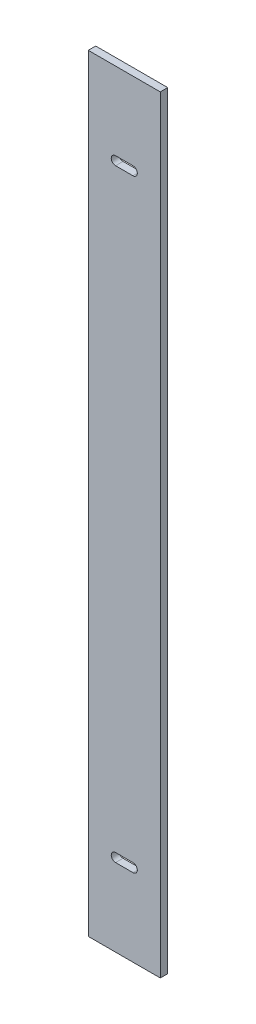
SolidWorks part; units mm, degrees
ref_plane "Plan de face" through (0, 0, 0) normal (0, 0, 1) x (1, 0, 0)
ref_plane "Plan de dessus" through (0, 0, 0) normal (0, 1, 0) x (1, 0, 0)
ref_plane "Plan de droite" through (0, 0, 0) normal (1, 0, 0) x (0, 0, -1)
sketch "Esquisse1" plane through (0, 0, 0) normal (0, 0, 1) x (1, 0, 0)
  line L0 (0, 154.5) -> (0, -154.5) construction
  line L1 (14.5, 154.5) -> (-14.5, 154.5)
  line L2 (14.5, 154.5) -> (14.5, -154.5)
  line L3 (14.5, -154.5) -> (-14.5, -154.5)
  line L4 (-14.5, 154.5) -> (-14.5, -154.5)
  line L5 (14.5, 154.5) -> (-14.5, -154.5) construction
  line L6 (14.5, -154.5) -> (-14.5, 154.5) construction
  line L7 (-14.5, 0) -> (14.5, 0) construction
  line L8 (-3.5, 121.5) -> (3.5, 121.5) construction
  line L9 (-3.5, 123.25) -> (3.5, 123.25)
  line L10 (-3.5, 119.75) -> (3.5, 119.75)
  line L14 (-3.5, -121.5) -> (3.5, -121.5) construction
  line L15 (-3.5, -123.25) -> (3.5, -123.25)
  line L16 (-3.5, -119.75) -> (3.5, -119.75)
  circle A0 centre (0, 121.5) radius 1.75 construction
  circle A1 centre (0, -121.5) radius 1.75 construction
  arc A2 (-3.5, 123.25) -> (-3.5, 119.75) centre (-3.5, 121.5) ccw
  arc A3 (3.5, 119.75) -> (3.5, 123.25) centre (3.5, 121.5) ccw
  arc A6 (-3.5, -123.25) -> (-3.5, -119.75) centre (-3.5, -121.5) cw
  arc A7 (3.5, -119.75) -> (3.5, -123.25) centre (3.5, -121.5) cw
  point P0 (0, 0)
  point P16 (0, 121.5)
  point P28 (0, 0)
  point P31 (0, -121.5)
  dimension "D3" = 3.5
  dimension "D6" = 1.75
  dimension "D1" = 29
  dimension "D2" = 309
  dimension "D4" = 33
  dimension "D5" = 7
extrude "Boss.-Extru.1" add sketch "Esquisse1" along normal blind 3
